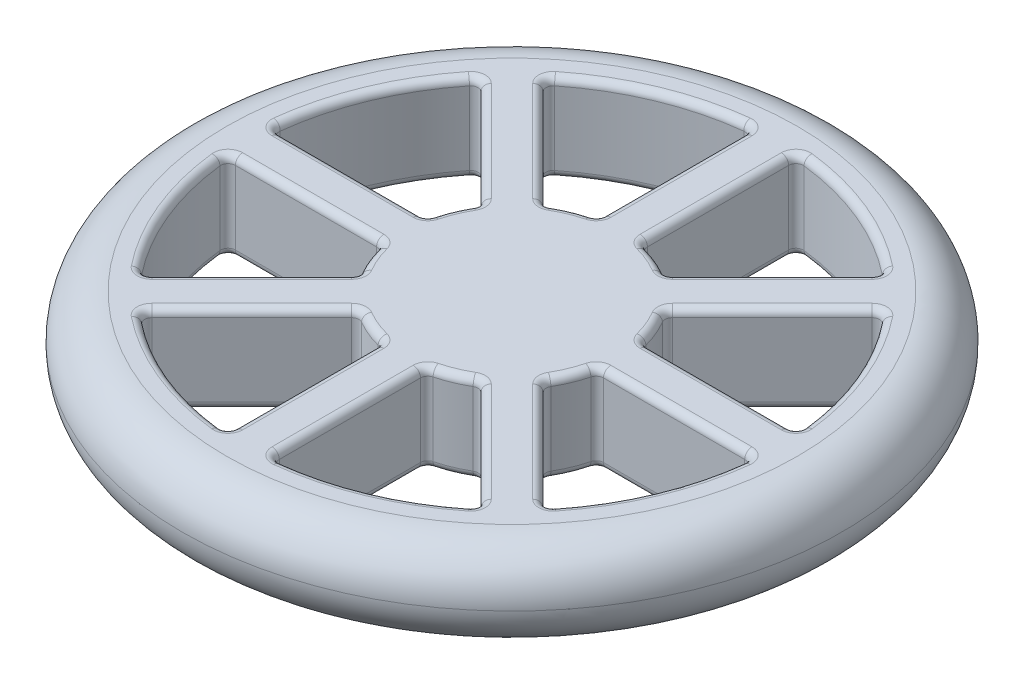
SolidWorks part; units mm, degrees
ref_plane "Front Plane" through (0, 0, 0) normal (0, 0, 1) x (1, 0, 0)
ref_plane "Top Plane" through (0, 0, 0) normal (0, 1, 0) x (1, 0, 0)
ref_plane "Right Plane" through (0, 0, 0) normal (1, 0, 0) x (0, 0, -1)
sketch "Sketch1" plane through (0, 0, 0) normal (0, 1, 0) x (1, 0, 0)
  circle A0 centre (0, 0) radius 22.5
  dimension "D1" = 45
extrude "Boss-Extrude1" add sketch "Sketch1" along normal blind 3 and the other way blind 3
fillet "Fillet1" radius 3 2 edges at (0, -3, 22.5) (0, 3, 22.5)
sketch "Sketch2" plane through (0, -3, 0) normal (0, -1, 0) x (1, 0, 0)
  line L1 (1.5, 17.9374) -> (1.5, 7.3485)
  line L3 (4.1355, 6.2568) -> (11.623, 13.7443)
  arc A3 (4.1355, 6.2568) -> (1.5, 7.3485) centre (0, 0) ccw
  arc A4 (11.623, 13.7443) -> (1.5, 17.9374) centre (0, 0) ccw
extrude "Cut-Extrude1" cut sketch "Sketch2" against normal up to next
fillet "Fillet2" radius 0.5 12 edges at (1.5, 0, 7.3485) (4.1355, 0, 6.2568) (11.623, 0, 13.7443) (1.5, 0, 17.9374) (1.5, 3, 12.6429) (2.8701, 3, 6.9291) (6.8883, 3, 16.6298) (7.8792, 3, 10.0006) (7.8792, -3, 10.0006) (2.8701, -3, 6.9291) (6.8883, -3, 16.6298) (1.5, -3, 12.6429)
sketch "Sketch3" plane through (0, 0, 0) normal (1, 0, 0) x (0, 0, -1)
  line L0 (0, 3) -> (0, -7.3813) construction
  line L1 (19.5, 3) -> (-19.5, 3) construction
pattern_circular "CirPattern1" count 8 over 360 about axis through (0, 3, 0) along (0, -1, 0) of "Cut-Extrude1", "Fillet2" reverse direction yes
